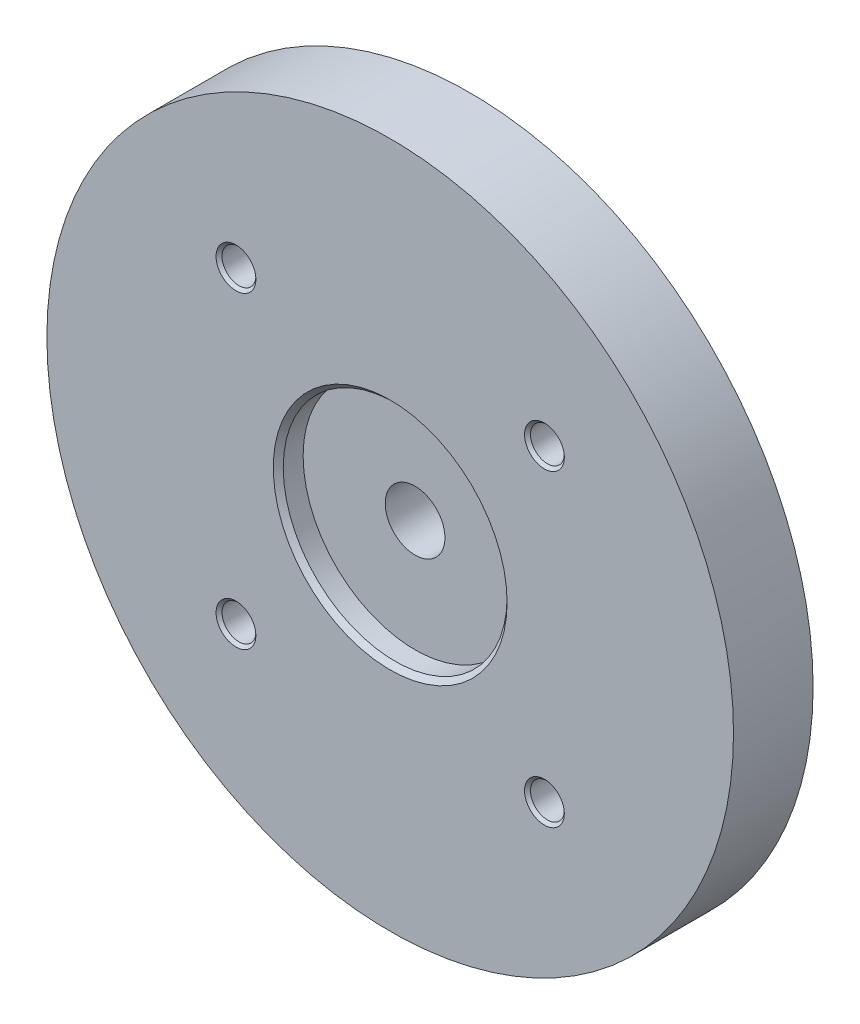
SolidWorks part; units mm, degrees
ref_plane "Front Plane" through (0, 0, 0) normal (0, 0, 1) x (1, 0, 0)
ref_plane "Top Plane" through (0, 0, 0) normal (0, 1, 0) x (1, 0, 0)
ref_plane "Right Plane" through (0, 0, 0) normal (1, 0, 0) x (0, 0, -1)
sketch "Sketch2" plane through (0, 0, 0) normal (0, 0, 1) x (1, 0, 0)
  circle A0 centre (0, 0) radius 34.5
  dimension "D1" = 69
extrude "Boss-Extrude1" add sketch "Sketch2" along normal blind 8
sketch "Sketch6" plane through (0, 0, 0) normal (0, 0, -1) x (-1, 0, 0)
  circle A0 centre (0, 0) radius 10
  dimension "D1" = 20
extrude "Boss-Extrude2" add sketch "Sketch6" along normal blind 2
sketch "Sketch3" plane through (0, 0, 8) normal (0, 0, 1) x (1, 0, 0)
  line L0 (0, -15.5) -> (0, 15.5) construction
  line L1 (15.5, 15.5) -> (-15.5, 15.5) construction
  line L2 (15.5, -15.5) -> (-15.5, -15.5) construction
  circle A0 centre (-15.5, 15.5) radius 1.7
  circle A1 centre (15.5, 15.5) radius 1.7
  circle A2 centre (15.5, -15.5) radius 1.7
  circle A3 centre (-15.5, -15.5) radius 1.7
  circle A4 centre (0, 0) radius 3
  point P12 (0, 0)
  point P16 (0, 15.5)
  point P19 (0, -15.5)
  dimension "D1" = 3.4
  dimension "D2" = 3.4
  dimension "D3" = 3.4
  dimension "D4" = 3.4
  dimension "D8" = 6
  dimension "D5" = 31
  dimension "D6" = 31
  dimension "D7" = 31
extrude "Cut-Extrude1" cut sketch "Sketch3" against normal through all both and the other way through all
sketch "Sketch4" plane through (0, 0, 0) normal (0, 0, -1) x (-1, 0, 0)
  circle A0 centre (-15.5, 15.5) radius 2.8
  circle A1 centre (15.5, 15.5) radius 2.8
  circle A2 centre (15.5, -15.5) radius 2.8
  circle A3 centre (-15.5, -15.5) radius 2.8
  dimension "D1" = 5.6
  dimension "D2" = 5.6
  dimension "D3" = 5.6
  dimension "D4" = 5.6
extrude "Cut-Extrude2" cut sketch "Sketch4" against normal blind 3 and the other way through all
sketch "Sketch5" plane through (0, 0, 0) normal (0, 0, -1) x (-1, 0, 0)
  circle A0 centre (0, 30) radius 2.1
  circle A1 centre (30, 0) radius 2.1
  circle A2 centre (0, -30) radius 2.1
  circle A3 centre (-30, 0) radius 2.1
  circle A4 centre (0, 0) radius 30 construction
  point P4 (30, 0)
  dimension "D1" = 4.2
  dimension "D2" = 60
  dimension "D3" = 4
extrude "Cut-Extrude3" cut sketch "Sketch5" against normal blind 6
fillet "Fillet1" radius 1 1 edges at (-10, 0, 0)
sketch "Sketch7" plane through (0, 0, 8) normal (0, 0, 1) x (1, 0, 0)
  circle A0 centre (0, 0) radius 11.25
  dimension "D1" = 22.5
extrude "Cut-Extrude4" cut sketch "Sketch7" against normal blind 2.5
chamfer "Chamfer1" distance 0.5 angle 45 1 edges at (11.25, 0, 8)
chamfer "Chamfer2" distance 0.3 angle 45 4 edges at (-13.8, -15.5, 8) (17.2, -15.5, 8) (17.2, 15.5, 8) (-13.8, 15.5, 8)
equation "\"N_pins\"= 26"
equation "\"N_lobes\"= \"N_pins\" - 1"
equation "\"R_pc\"= 25"
equation "\"D_pin\"= 3"
equation "\"R_pin\"= \"D_pin\" / 2"
equation "\"ecc\"= 0.72"
equation "\"t_disc\"= 7"
equation "\"N_out\"= 8"
equation "\"D_outc\"=22"
equation "\"D_roller\"= 5"
equation "\"D_outhole\"= \"D_roller\" + 2 * \"ecc\""
equation "\"D_cam_OD\"= 21"
equation "\"D_cam_ID\"= 10"
equation "\"clr_bore\"= 1"
equation "\"D_bore\"= 2 * \"R_pc\" + \"clr_bore\""
equation "\"t_wall\"= 7.5"
equation "\"D_housing\"= 69"
equation "\"D1@Sketch2\"=\"D_housing\""
